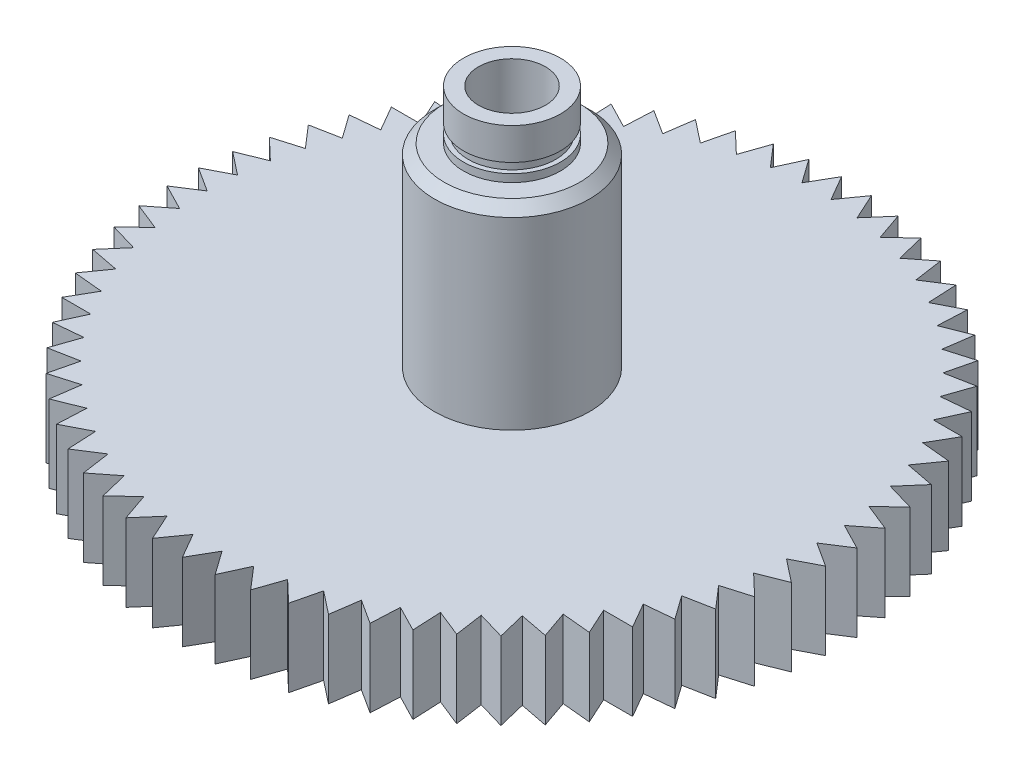
SolidWorks part; units mm, degrees
ref_plane "Front Plane" through (0, 0, 0) normal (0, 0, 1) x (1, 0, 0)
ref_plane "Top Plane" through (0, 0, 0) normal (0, 1, 0) x (1, 0, 0)
ref_plane "Right Plane" through (0, 0, 0) normal (1, 0, 0) x (0, 0, -1)
sketch "Sketch1" plane through (0, 0, 0) normal (0, 1, 0) x (1, 0, 0)
  line L1 (0, 17) -> (0.7481, 15.7043)
  line L2 (0, 17) -> (-0.7481, 15.7043)
  line L3 (1.616, 16.923) -> (2.2375, 15.5621)
  line L4 (1.616, 16.923) -> (0.7481, 15.7043)
  line L6 (3.2173, 16.6928) -> (3.7066, 15.2789)
  line L7 (3.2173, 16.6928) -> (2.2375, 15.5621)
  line L9 (4.7895, 16.3114) -> (5.1422, 14.8574)
  line L10 (4.7895, 16.3114) -> (3.7066, 15.2789)
  line L12 (6.3183, 15.7823) -> (6.5312, 14.3013)
  line L13 (6.3183, 15.7823) -> (5.1422, 14.8574)
  line L15 (7.7899, 15.1102) -> (7.861, 13.6157)
  line L16 (7.7899, 15.1102) -> (6.5312, 14.3013)
  line L18 (9.1909, 14.3013) -> (9.1197, 12.8068)
  line L19 (9.1909, 14.3013) -> (7.861, 13.6157)
  line L21 (10.5087, 13.3629) -> (10.2958, 11.882)
  line L22 (10.5087, 13.3629) -> (9.1197, 12.8068)
  line L24 (11.7313, 12.3035) -> (11.3786, 10.8495)
  line L25 (11.7313, 12.3035) -> (10.2958, 11.882)
  line L27 (12.8477, 11.1326) -> (12.3584, 9.7187)
  line L28 (12.8477, 11.1326) -> (11.3786, 10.8495)
  line L30 (13.8478, 9.861) -> (13.2263, 8.5)
  line L31 (13.8478, 9.861) -> (12.3584, 9.7187)
  line L33 (14.7224, 8.5) -> (13.9743, 7.2043)
  line L34 (14.7224, 8.5) -> (13.2263, 8.5)
  line L36 (15.4637, 7.0621) -> (14.5959, 5.8433)
  line L37 (15.4637, 7.0621) -> (13.9743, 7.2043)
  line L39 (16.065, 5.5602) -> (15.0852, 4.4294)
  line L40 (16.065, 5.5602) -> (14.5959, 5.8433)
  line L42 (16.5208, 4.0079) -> (15.438, 2.9754)
  line L43 (16.5208, 4.0079) -> (15.0852, 4.4294)
  line L45 (16.827, 2.4194) -> (15.6509, 1.4945)
  line L46 (16.827, 2.4194) -> (15.438, 2.9754)
  line L48 (16.9807, 0.8089) -> (15.7221, 0)
  line L49 (16.9807, 0.8089) -> (15.6509, 1.4945)
  line L51 (16.9807, -0.8089) -> (15.6509, -1.4945)
  line L52 (16.9807, -0.8089) -> (15.7221, 0)
  line L54 (16.827, -2.4194) -> (15.438, -2.9754)
  line L55 (16.827, -2.4194) -> (15.6509, -1.4945)
  line L57 (16.5208, -4.0079) -> (15.0852, -4.4294)
  line L58 (16.5208, -4.0079) -> (15.438, -2.9754)
  line L60 (16.065, -5.5602) -> (14.5959, -5.8433)
  line L61 (16.065, -5.5602) -> (15.0852, -4.4294)
  line L63 (15.4637, -7.0621) -> (13.9743, -7.2043)
  line L64 (15.4637, -7.0621) -> (14.5959, -5.8433)
  line L66 (14.7224, -8.5) -> (13.2263, -8.5)
  line L67 (14.7224, -8.5) -> (13.9743, -7.2043)
  line L69 (13.8478, -9.861) -> (12.3584, -9.7187)
  line L70 (13.8478, -9.861) -> (13.2263, -8.5)
  line L72 (12.8477, -11.1326) -> (11.3786, -10.8495)
  line L73 (12.8477, -11.1326) -> (12.3584, -9.7187)
  line L75 (11.7313, -12.3035) -> (10.2958, -11.882)
  line L76 (11.7313, -12.3035) -> (11.3786, -10.8495)
  line L78 (10.5087, -13.3629) -> (9.1197, -12.8068)
  line L79 (10.5087, -13.3629) -> (10.2958, -11.882)
  line L81 (9.1909, -14.3013) -> (7.861, -13.6157)
  line L82 (9.1909, -14.3013) -> (9.1197, -12.8068)
  line L84 (7.7899, -15.1102) -> (6.5312, -14.3013)
  line L85 (7.7899, -15.1102) -> (7.861, -13.6157)
  line L87 (6.3183, -15.7823) -> (5.1422, -14.8574)
  line L88 (6.3183, -15.7823) -> (6.5312, -14.3013)
  line L90 (4.7895, -16.3114) -> (3.7066, -15.2789)
  line L91 (4.7895, -16.3114) -> (5.1422, -14.8574)
  line L93 (3.2173, -16.6928) -> (2.2375, -15.5621)
  line L94 (3.2173, -16.6928) -> (3.7066, -15.2789)
  line L96 (1.616, -16.923) -> (0.7481, -15.7043)
  line L97 (1.616, -16.923) -> (2.2375, -15.5621)
  line L99 (0, -17) -> (-0.7481, -15.7043)
  line L100 (0, -17) -> (0.7481, -15.7043)
  line L102 (-1.616, -16.923) -> (-2.2375, -15.5621)
  line L103 (-1.616, -16.923) -> (-0.7481, -15.7043)
  line L105 (-3.2173, -16.6928) -> (-3.7066, -15.2789)
  line L106 (-3.2173, -16.6928) -> (-2.2375, -15.5621)
  line L108 (-4.7895, -16.3114) -> (-5.1422, -14.8574)
  line L109 (-4.7895, -16.3114) -> (-3.7066, -15.2789)
  line L111 (-6.3183, -15.7823) -> (-6.5312, -14.3013)
  line L112 (-6.3183, -15.7823) -> (-5.1422, -14.8574)
  line L114 (-7.7899, -15.1102) -> (-7.861, -13.6157)
  line L115 (-7.7899, -15.1102) -> (-6.5312, -14.3013)
  line L117 (-9.1909, -14.3013) -> (-9.1197, -12.8068)
  line L118 (-9.1909, -14.3013) -> (-7.861, -13.6157)
  line L120 (-10.5087, -13.3629) -> (-10.2958, -11.882)
  line L121 (-10.5087, -13.3629) -> (-9.1197, -12.8068)
  line L123 (-11.7313, -12.3035) -> (-11.3786, -10.8495)
  line L124 (-11.7313, -12.3035) -> (-10.2958, -11.882)
  line L126 (-12.8477, -11.1326) -> (-12.3584, -9.7187)
  line L127 (-12.8477, -11.1326) -> (-11.3786, -10.8495)
  line L129 (-13.8478, -9.861) -> (-13.2263, -8.5)
  line L130 (-13.8478, -9.861) -> (-12.3584, -9.7187)
  line L132 (-14.7224, -8.5) -> (-13.9743, -7.2043)
  line L133 (-14.7224, -8.5) -> (-13.2263, -8.5)
  line L135 (-15.4637, -7.0621) -> (-14.5959, -5.8433)
  line L136 (-15.4637, -7.0621) -> (-13.9743, -7.2043)
  line L138 (-16.065, -5.5602) -> (-15.0852, -4.4294)
  line L139 (-16.065, -5.5602) -> (-14.5959, -5.8433)
  line L141 (-16.5208, -4.0079) -> (-15.438, -2.9754)
  line L142 (-16.5208, -4.0079) -> (-15.0852, -4.4294)
  line L144 (-16.827, -2.4194) -> (-15.6509, -1.4945)
  line L145 (-16.827, -2.4194) -> (-15.438, -2.9754)
  line L147 (-16.9807, -0.8089) -> (-15.7221, 0)
  line L148 (-16.9807, -0.8089) -> (-15.6509, -1.4945)
  line L150 (-16.9807, 0.8089) -> (-15.6509, 1.4945)
  line L151 (-16.9807, 0.8089) -> (-15.7221, 0)
  line L153 (-16.827, 2.4194) -> (-15.438, 2.9754)
  line L154 (-16.827, 2.4194) -> (-15.6509, 1.4945)
  line L156 (-16.5208, 4.0079) -> (-15.0852, 4.4294)
  line L157 (-16.5208, 4.0079) -> (-15.438, 2.9754)
  line L159 (-16.065, 5.5602) -> (-14.5959, 5.8433)
  line L160 (-16.065, 5.5602) -> (-15.0852, 4.4294)
  line L162 (-15.4637, 7.0621) -> (-13.9743, 7.2043)
  line L163 (-15.4637, 7.0621) -> (-14.5959, 5.8433)
  line L165 (-14.7224, 8.5) -> (-13.2263, 8.5)
  line L166 (-14.7224, 8.5) -> (-13.9743, 7.2043)
  line L168 (-13.8478, 9.861) -> (-12.3584, 9.7187)
  line L169 (-13.8478, 9.861) -> (-13.2263, 8.5)
  line L171 (-12.8477, 11.1326) -> (-11.3786, 10.8495)
  line L172 (-12.8477, 11.1326) -> (-12.3584, 9.7187)
  line L174 (-11.7313, 12.3035) -> (-10.2958, 11.882)
  line L175 (-11.7313, 12.3035) -> (-11.3786, 10.8495)
  line L177 (-10.5087, 13.3629) -> (-9.1197, 12.8068)
  line L178 (-10.5087, 13.3629) -> (-10.2958, 11.882)
  line L180 (-9.1909, 14.3013) -> (-7.861, 13.6157)
  line L181 (-9.1909, 14.3013) -> (-9.1197, 12.8068)
  line L183 (-7.7899, 15.1102) -> (-6.5312, 14.3013)
  line L184 (-7.7899, 15.1102) -> (-7.861, 13.6157)
  line L186 (-6.3183, 15.7823) -> (-5.1422, 14.8574)
  line L187 (-6.3183, 15.7823) -> (-6.5312, 14.3013)
  line L189 (-4.7895, 16.3114) -> (-3.7066, 15.2789)
  line L190 (-4.7895, 16.3114) -> (-5.1422, 14.8574)
  line L192 (-3.2173, 16.6928) -> (-2.2375, 15.5621)
  line L193 (-3.2173, 16.6928) -> (-3.7066, 15.2789)
  line L195 (-1.616, 16.923) -> (-0.7481, 15.7043)
  line L196 (-1.616, 16.923) -> (-2.2375, 15.5621)
  point P336 (0, 0)
  dimension "D2" = 66
extrude "Boss-Extrude1" add sketch "Sketch1" along normal blind 4
sketch "Sketch2" plane through (0, 4, 0) normal (0, 1, 0) x (1, 0, 0)
  circle A0 centre (0, 0) radius 4
  dimension "D1" = 8
extrude "Boss-Extrude2" add sketch "Sketch2" along normal blind 12.55
sketch "Sketch3" plane through (0, 16.55, 0) normal (0, 1, 0) x (1, 0, 0)
  circle A0 centre (0, 0) radius 2.5
  circle A1 centre (0, 0) radius 4
  dimension "D1" = 5
extrude "Cut-Extrude1" cut sketch "Sketch3" against normal blind 2.55
sketch "Sketch4" plane through (0, 16.55, 0) normal (0, 1, 0) x (1, 0, 0)
  circle A0 centre (0, 0) radius 1.725
  dimension "D1" = 3.45
extrude "Cut-Extrude2" cut sketch "Sketch4" against normal up to next
sketch "Sketch5" plane through (0, 16.55, 0) normal (0, 1, 0) x (1, 0, 0)
  circle A0 centre (0, 0) radius 2.5
  circle A1 centre (0, 0) radius 2.2597
extrude "Cut-Extrude3" cut sketch "Sketch5" against normal blind 0.5 from offset 1.65 offset against normal yes
chamfer "Chamfer1" distance 0.5 angle 45 1 edges at (0, 14, 4)
sketch "Sketch6" plane through (0, 0, 0) normal (0, -1, 0) x (-1, 0, 0)
  circle A0 centre (0, 0) radius 3.0647
  circle A1 centre (0, 0) radius 1.725
extrude "Boss-Extrude3" add sketch "Sketch6" along normal blind 3.65
sketch "Sketch7" plane through (0, -3.65, 0) normal (0, -1, 0) x (-1, 0, 0)
  circle A0 centre (0, 0) radius 3.0647
  circle A1 centre (0, 0) radius 2.5
  circle A2 centre (0, 0) radius 3.0647 construction
  dimension "D1" = 5
extrude "Cut-Extrude5" cut sketch "Sketch7" against normal blind 2.5
sketch "Sketch8" plane through (0, -3.65, 0) normal (0, -1, 0) x (1, 0, 0)
  circle A0 centre (0, 0) radius 2.2597
  circle A1 centre (0, 0) radius 2.5
extrude "Cut-Extrude6" cut sketch "Sketch8" against normal blind 0.5 from offset 1.65 offset against normal yes
sketch "Sketch9" plane through (0, 0, 0) normal (0, -1, 0) x (1, 0, 0)
  circle A0 centre (0, 0) radius 4
  dimension "D1" = 8
extrude "Boss-Extrude4" add sketch "Sketch9" along normal up to surface (1.15 mm away) up to face at (0, -1.15, -2.5)
